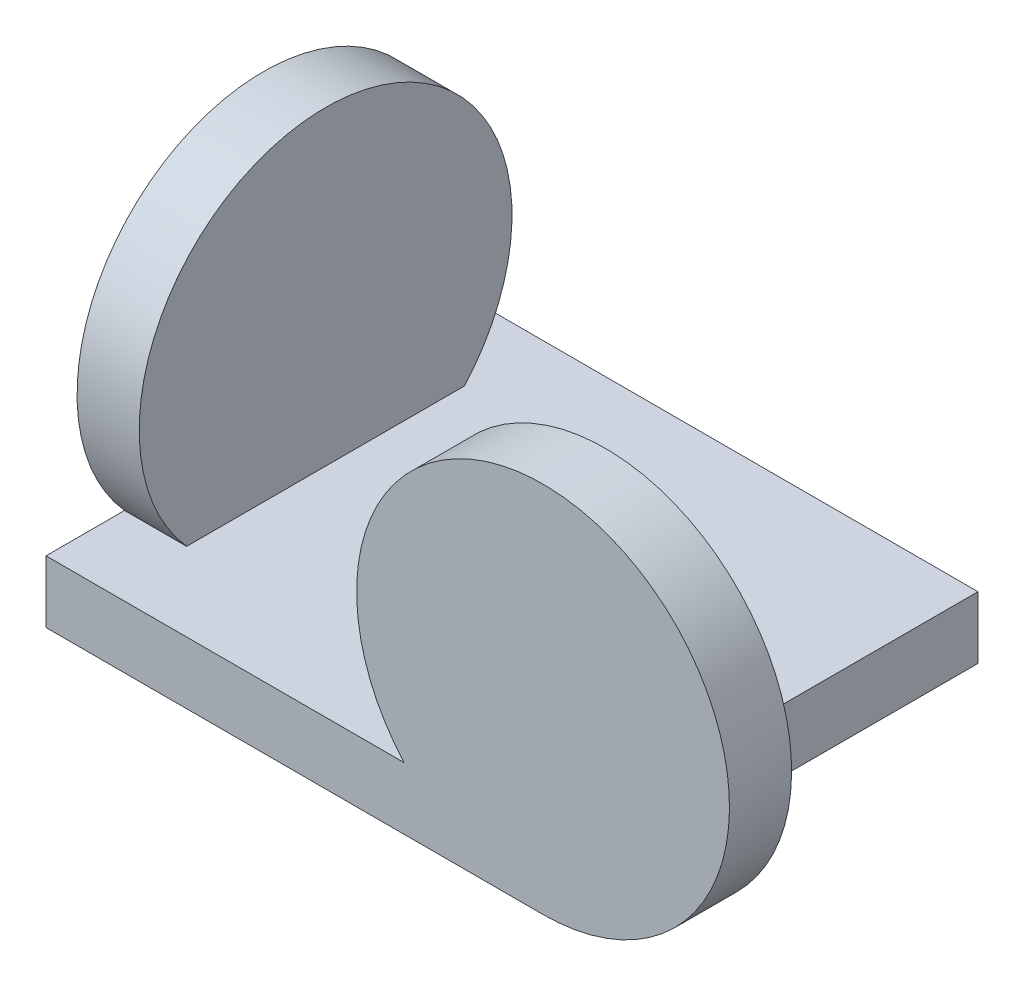
SolidWorks part; units mm, degrees
ref_plane "Front Plane" through (0, 0, 0) normal (0, 0, 1) x (1, 0, 0)
ref_plane "Top Plane" through (0, 0, 0) normal (0, 1, 0) x (1, 0, 0)
ref_plane "Right Plane" through (0, 0, 0) normal (1, 0, 0) x (0, 0, -1)
sketch "Sketch1" plane through (0, 0, 0) normal (0, 0, 1) x (1, 0, 0)
  circle A0 centre (0, 0) radius 30
  dimension "D1" = 60
extrude "Boss-Extrude1" add sketch "Sketch1" along normal blind 10 contours A0
sketch "Sketch2" plane through (0, 0, 10) normal (0, 0, 1) x (1, 0, 0)
  line L1 (0, -30) -> (-80, -30)
  line L2 (0, -30) -> (0, -20)
  line L3 (0, -20) -> (-80, -20)
  line L4 (-80, -30) -> (-80, -20)
  circle A0 centre (0, 0) radius 30 construction
  dimension "D1" = 10
  dimension "D2" = 80
extrude "Boss-Extrude2" add sketch "Sketch2" against normal blind 70
sketch "Sketch3" plane through (-80, 0, 0) normal (-1, 0, 0) x (0, 0, 1)
  line L1 (-60, -20) -> (10, -20) construction
  line L2 (-60, -30) -> (10, -30) construction
  circle A1 centre (-25, 0) radius 30
  point P2 (0, 0)
  point P5 (-25, -20)
  dimension "D1" = 60
extrude "Boss-Extrude3" add sketch "Sketch3" against normal blind 10 contours A1
